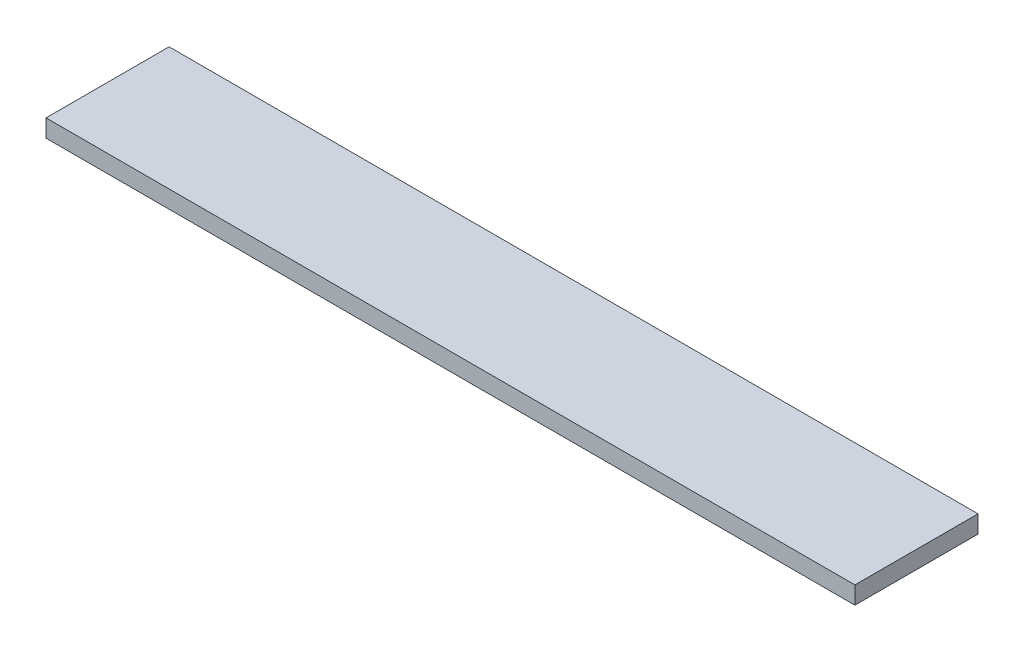
SolidWorks part; units mm, degrees
ref_plane "Front Plane" through (0, 0, 0) normal (0, 0, 1) x (1, 0, 0)
ref_plane "Top Plane" through (0, 0, 0) normal (0, 1, 0) x (1, 0, 0)
ref_plane "Right Plane" through (0, 0, 0) normal (1, 0, 0) x (0, 0, -1)
sketch "Sketch1" plane through (0, 0, 0) normal (0, 1, 0) x (1, 0, 0)
  line L0 (0, -55) -> (0, 55) construction
  line L1 (-115, 17.5) -> (115, 17.5)
  line L2 (-115, 17.5) -> (-115, -17.5)
  line L3 (-115, -17.5) -> (115, -17.5)
  line L4 (115, 17.5) -> (115, -17.5)
  line L5 (-55, 0) -> (55, 0) construction
  point P4 (0, 17.5)
  point P7 (-115, 0)
  dimension "D1" = 230
  dimension "D2" = 35
extrude "Boss-Extrude1" add sketch "Sketch1" along normal mid plane 5
